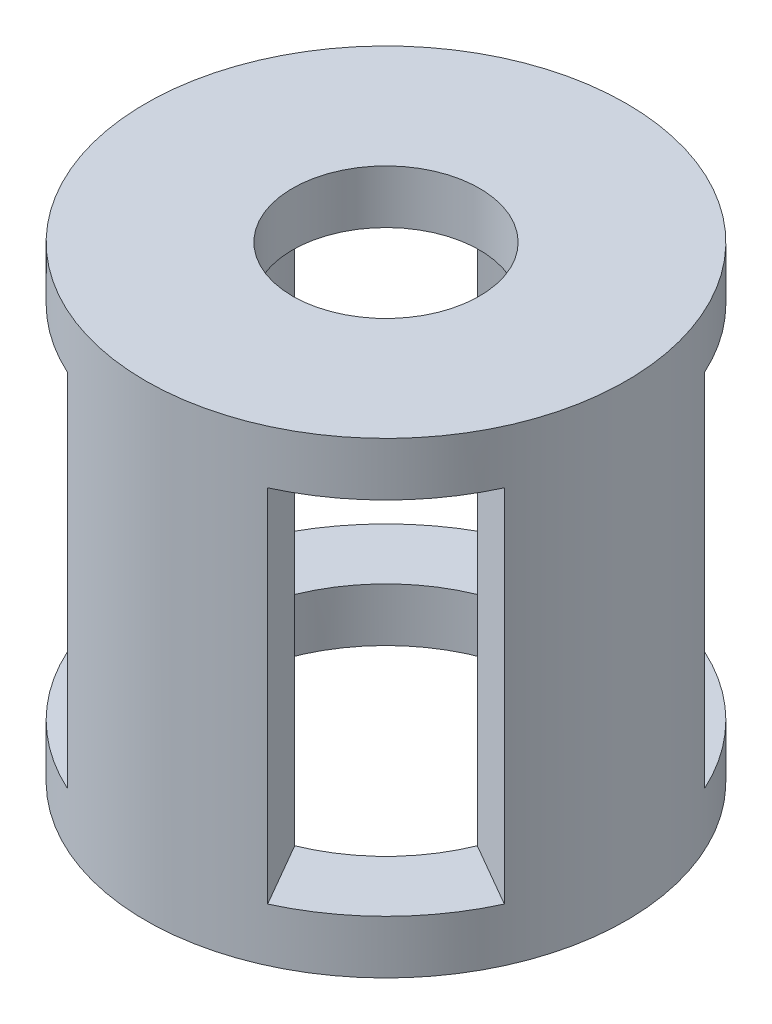
SolidWorks part; units mm, degrees
ref_plane "Front Plane" through (0, 0, 0) normal (0, 0, 1) x (1, 0, 0)
ref_plane "Top Plane" through (0, 0, 0) normal (0, 1, 0) x (1, 0, 0)
ref_plane "Right Plane" through (0, 0, 0) normal (1, 0, 0) x (0, 0, -1)
sketch "Sketch1" plane through (0, 0, 0) normal (0, 1, 0) x (1, 0, 0)
  circle A0 centre (0, 0) radius 18
  circle A1 centre (0, 0) radius 7
  dimension "D1" = 36
  dimension "D2" = 14
extrude "Boss-Extrude1" add sketch "Sketch1" along normal blind 4
sketch "Sketch2" plane through (0, 0, 0) normal (0, -1, 0) x (1, 0, 0)
  line L0 (0, 0) -> (50000, 0) construction
  line L1 (0, 1.3656) -> (0, 50001.3656) construction
  line L2 (4.7324, 11.5695) -> (7.5, 16.3631)
  line L3 (-4.7324, 11.5695) -> (-7.5, 16.3631)
  line L4 (11.5695, -4.7324) -> (16.3631, -7.5)
  line L5 (11.5695, 4.7324) -> (16.3631, 7.5)
  line L6 (-4.7324, -11.5695) -> (-7.5, -16.3631)
  line L7 (4.7324, -11.5695) -> (7.5, -16.3631)
  line L8 (-11.5695, 4.7324) -> (-16.3631, 7.5)
  line L9 (-11.5695, -4.7324) -> (-16.3631, -7.5)
  arc A0 (0, -10) -> (-10, 0) centre (0, 0) ccw construction
  arc A2 (4.7324, 11.5695) -> (-4.7324, 11.5695) centre (0, 0) ccw
  circle A5 centre (0, 0) radius 18 construction
  arc A6 (7.5, 16.3631) -> (-7.5, 16.3631) centre (0, 0) ccw
  arc A7 (11.5695, -4.7324) -> (11.5695, 4.7324) centre (0, 0) ccw
  arc A8 (16.3631, -7.5) -> (16.3631, 7.5) centre (0, 0) ccw
  arc A9 (-4.7324, -11.5695) -> (4.7324, -11.5695) centre (0, 0) ccw
  arc A10 (-7.5, -16.3631) -> (7.5, -16.3631) centre (0, 0) ccw
  arc A11 (-11.5695, 4.7324) -> (-11.5695, -4.7324) centre (0, 0) ccw
  arc A12 (-16.3631, 7.5) -> (-16.3631, -7.5) centre (0, 0) ccw
  point P28 (0, 0)
  dimension "D1" = 20
  dimension "D2" = 2.5
  dimension "D3" = 15
  dimension "D4" = 30
  dimension "D5" = 4
extrude "Boss-Extrude2" add sketch "Sketch2" along normal blind 30
sketch "Sketch3" plane through (0, -30, 0) normal (0, -1, 0) x (1, 0, 0)
  circle A0 centre (0, 0) radius 12.5
  circle A1 centre (0, 0) radius 18
extrude "Boss-Extrude3" add sketch "Sketch3" against normal blind 3 and the other way blind 1
